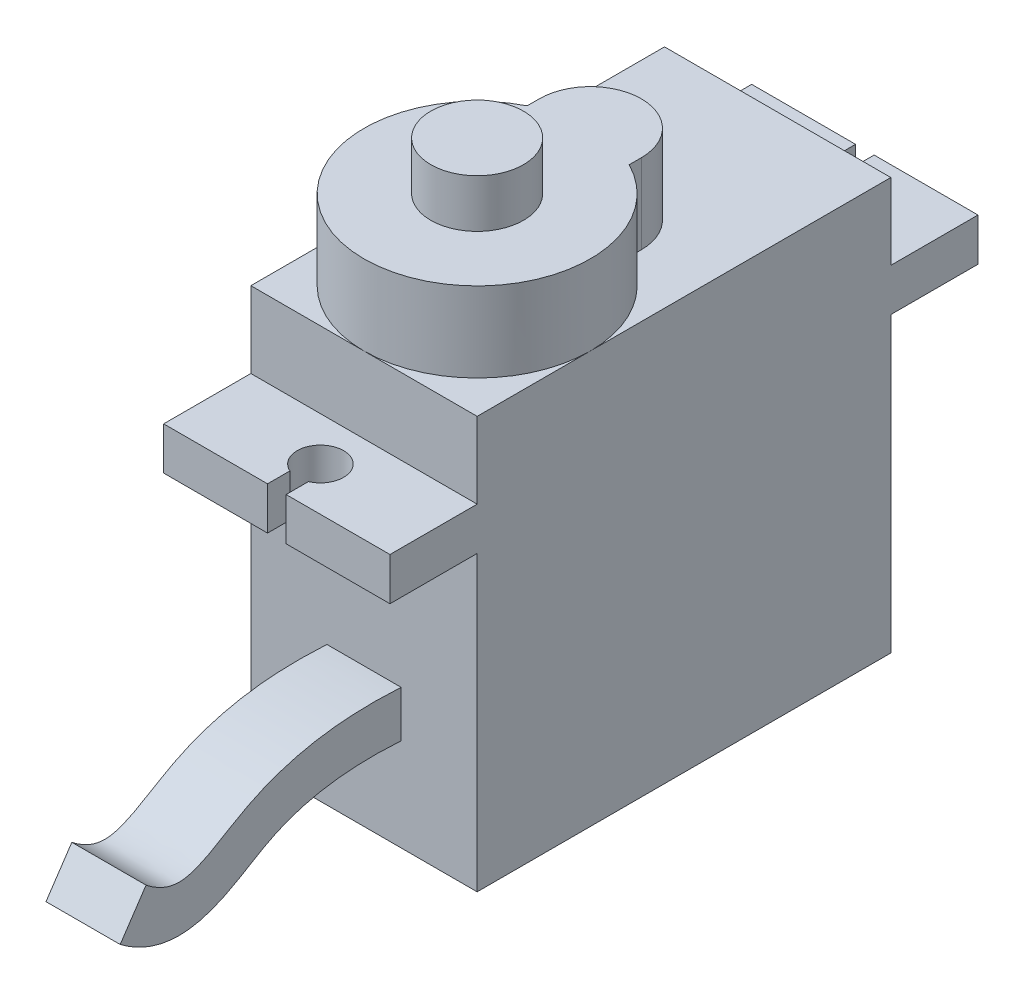
SolidWorks part; units mm, degrees
ref_plane "Спереди" through (0, 0, 0) normal (0, 0, 1) x (1, 0, 0)
ref_plane "Сверху" through (0, 0, 0) normal (0, 1, 0) x (1, 0, 0)
ref_plane "Справа" through (0, 0, 0) normal (1, 0, 0) x (0, 0, -1)
sketch "Эскиз1" plane through (0, 0, 0) normal (1, 0, 0) x (0, 0, -1)
  line L0 (11.15, 22.2) -> (11.15, 18.1) construction
  line L1 (0, 0) -> (22.3, 0)
  line L2 (0, 0) -> (0, 15.8)
  line L3 (0, 22.2) -> (22.3, 22.2)
  line L4 (22.3, 0) -> (22.3, 15.8)
  line L5 (11.15, 18.1) -> (0, 18.1) construction
  line L6 (0, 18.1) -> (0, 22.2)
  line L7 (0, 18.1) -> (-4.7, 18.1)
  line L8 (22.3, 15.8) -> (27, 15.8)
  line L9 (0, 15.8) -> (-4.7, 15.8)
  line L10 (-4.7, 18.1) -> (-4.7, 15.8)
  line L11 (22.3, 18.1) -> (27, 18.1)
  line L12 (27, 18.1) -> (27, 15.8)
  line L13 (22.3, 18.1) -> (22.3, 22.2)
  dimension "D1" = 22.2
  dimension "D2" = 22.3
  dimension "D3" = 4.1
  dimension "D4" = 2.3
  dimension "D5" = 4.7
extrude "Бобышка-Вытянуть1" add sketch "Эскиз1" along normal mid plane 12.2
sketch "Эскиз2" plane through (0, 22.2, 0) normal (0, 1, 0) x (1, 0, 0)
  line L0 (0, 0) -> (0, 6.1) construction
  line L1 (0, 6.1) -> (6.1, 6.1) construction
  line L2 (6.1, 22.3) -> (6.1, 0) construction
  line L3 (-2.75, 12.2) -> (-2.75, 11.545)
  line L4 (2.75, 12.2) -> (2.75, 11.545)
  arc A0 (-2.75, 11.545) -> (2.75, 11.545) centre (0, 6.1) ccw
  arc A1 (2.75, 12.2) -> (-2.75, 12.2) centre (0, 12.2) ccw
  dimension "D1" = 5.5
extrude "Бобышка-Вытянуть2" add sketch "Эскиз2" along normal blind 4.3
sketch "Эскиз3" plane through (0, 26.5, 0) normal (0, 1, 0) x (1, 0, 0)
  line L0 (0, 0) -> (0, 14.95) construction
  line L1 (6.1, 6.1) -> (-6.1, 6.1) construction
  arc A0 (2.75, 12.2) -> (-2.75, 12.2) centre (0, 12.2) ccw construction
  arc A1 (-2.75, 11.545) -> (2.75, 11.545) centre (0, 6.1) ccw construction
  circle A2 centre (0, 6.1) radius 2.5
  dimension "D1" = 5
extrude "Бобышка-Вытянуть3" add sketch "Эскиз3" along normal blind 2.6
sketch "Эскиз4" plane through (0, 0, 0) normal (0, 0, -1) x (-1, 0, 0)
  line L0 (0, 0) -> (0, 5) construction
  line L1 (-2, 5) -> (-2, 7.5)
  line L2 (-2, 5) -> (2, 5)
  line L4 (-2, 7.5) -> (2, 7.5)
  line L5 (2, 5) -> (2, 7.5)
  dimension "D1" = 5
  dimension "D2" = 4
  dimension "D3" = 2.5
sketch "Эскиз5" plane through (0, 0, 0) normal (1, 0, 0) x (0, 0, -1)
  line L1 (11.15, 0) -> (11.15, 14.3676) construction
  line L2 (0, 0) -> (22.3, 0) construction
  spline S1 degree 3 poles (11.15, 4.494) (6.454, 5.232) (-0.4932, 7.1675) (-8.6212, 5.1515) (-11.6691, 2.0023) (-14.4339, 4.1204) knots 0.328952 0.328952 0.328952 0.328952 0.682877 0.808913 1 1 1 1
  point P17 (11.15, 14.3676)
sweep "По траектории1" add profiles "Эскиз4" path "Эскиз5"
sketch "Эскиз6" plane through (0, 18.1, 0) normal (0, 1, 0) x (1, 0, 0)
  line L0 (0, 27) -> (0, 22.3) construction
  line L1 (6.1, 27) -> (-6.1, 27) construction
  line L2 (6.1, 22.3) -> (-6.1, 22.3) construction
  line L3 (-6.1, 24.65) -> (6.1, 24.65) construction
  line L4 (-6.1, 27) -> (-6.1, 22.3) construction
  line L5 (6.1, 27) -> (6.1, 22.3) construction
  line L6 (-0.5, 27) -> (-0.5, 25.7956)
  line L7 (0, 27) -> (0.5, 27)
  line L8 (0, 27) -> (-0.5, 27)
  line L9 (-6.1, 22.3) -> (-6.1, 0) construction
  line L10 (0.5, 27) -> (0.5, 25.7956)
  line L11 (-6.1, 11.15) -> (6.1, 11.15) construction
  line L12 (6.1, 22.3) -> (6.1, 6.1) construction
  line L13 (0.5, -4.7) -> (0.5, -3.4956)
  line L14 (0, -4.7) -> (-0.5, -4.7)
  line L15 (0, -4.7) -> (0.5, -4.7)
  line L16 (-0.5, -4.7) -> (-0.5, -3.4956)
  arc A0 (-0.5, 25.7956) -> (0.5, 25.7956) centre (0, 24.65) ccw
  arc A1 (-0.5, -3.4956) -> (0.5, -3.4956) centre (0, -2.35) cw
  point P32 (0, -2.35)
  point P33 (0, 24.65)
  dimension "D1" = 2.5
  dimension "D2" = 0.5
extrude "Вырез-Вытянуть1" cut sketch "Эскиз6" against normal blind 3
